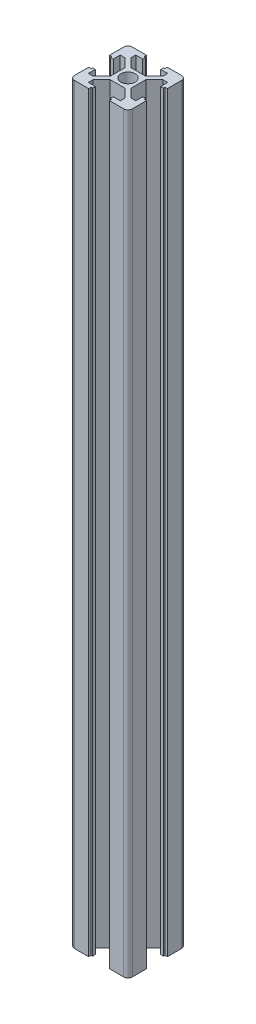
SolidWorks part; units mm, degrees
ref_plane "前视基准面" through (0, 0, 0) normal (0, 0, 1) x (1, 0, 0)
ref_plane "上视基准面" through (0, 0, 0) normal (0, 1, 0) x (1, 0, 0)
ref_plane "右视基准面" through (0, 0, 0) normal (1, 0, 0) x (0, 0, -1)
other "Configuration Table"
sketch "草图1" plane through (0, 0, 0) normal (0, 1, 0) x (1, 0, 0)
  line L0 (-4.4156, 1.3346) -> (-4.4156, 4.4346) construction
  line L1 (-4.4156, 3.874) -> (-4.4156, -1.2047)
  line L2 (1.7237, 4.9346) -> (-3.3549, 4.9346)
  line L3 (2.7844, -1.2047) -> (2.7844, 3.874)
  line L4 (-3.3549, -2.2654) -> (1.7237, -2.2654)
  line L5 (-10.8156, 1.3346) -> (9.1844, 1.3346) construction
  line L6 (-0.8156, 11.3346) -> (-0.8156, -8.6654) construction
  line L7 (-10.8156, 11.3346) -> (-0.8156, 1.3346) construction
  line L8 (-10.8156, 4.9346) -> (-4.4156, 4.9346) construction
  line L9 (-10.0156, 4.4346) -> (-3.9156, 4.4346) construction
  line L10 (-9.0156, 6.8346) -> (-6.3156, 6.8346) construction
  line L11 (-7.3763, 6.8346) -> (-4.4156, 3.874) construction
  line L12 (-10.8156, 9.8346) -> (-10.8156, 4.9346)
  line L13 (-10.8156, 4.9346) -> (-10.0156, 4.9346)
  line L14 (-10.0156, 4.9346) -> (-10.0156, 4.4346)
  line L15 (-10.0156, 4.4346) -> (-9.0156, 4.4346)
  line L16 (-9.0156, 4.4346) -> (-9.0156, 6.8346)
  line L17 (-9.0156, 6.8346) -> (-7.3763, 6.8346)
  line L18 (-7.3763, 6.8346) -> (-4.4156, 3.874)
  line L19 (-3.9156, 10.5346) -> (-3.9156, 9.5346)
  line L20 (-4.4156, 10.5346) -> (-3.9156, 10.5346)
  line L21 (-4.4156, 11.3346) -> (-4.4156, 10.5346)
  line L22 (-9.3156, 11.3346) -> (-4.4156, 11.3346)
  line L23 (-3.9156, 9.5346) -> (-6.3156, 9.5346)
  line L24 (-6.3156, 9.5346) -> (-6.3156, 7.8953)
  line L25 (-6.3156, 7.8953) -> (-3.3549, 4.9346)
  line L26 (9.1844, 11.3346) -> (-0.8156, 1.3346) construction
  line L27 (4.6844, 7.8953) -> (1.7237, 4.9346)
  line L28 (4.6844, 9.5346) -> (4.6844, 7.8953)
  line L29 (2.2844, 9.5346) -> (4.6844, 9.5346)
  line L30 (2.2844, 10.5346) -> (2.2844, 9.5346)
  line L31 (2.7844, 10.5346) -> (2.2844, 10.5346)
  line L32 (2.7844, 11.3346) -> (2.7844, 10.5346)
  line L33 (7.6844, 11.3346) -> (2.7844, 11.3346)
  line L34 (9.1844, 9.8346) -> (9.1844, 4.9346)
  line L35 (9.1844, 4.9346) -> (8.3844, 4.9346)
  line L36 (8.3844, 4.9346) -> (8.3844, 4.4346)
  line L37 (8.3844, 4.4346) -> (7.3844, 4.4346)
  line L38 (7.3844, 4.4346) -> (7.3844, 6.8346)
  line L39 (7.3844, 6.8346) -> (5.7451, 6.8346)
  line L40 (5.7451, 6.8346) -> (2.7844, 3.874)
  line L41 (9.1844, -8.6654) -> (-0.8156, 1.3346) construction
  line L42 (5.7451, -4.1654) -> (2.7844, -1.2047)
  line L43 (7.3844, -4.1654) -> (5.7451, -4.1654)
  line L44 (7.3844, -1.7654) -> (7.3844, -4.1654)
  line L45 (8.3844, -1.7654) -> (7.3844, -1.7654)
  line L46 (8.3844, -2.2654) -> (8.3844, -1.7654)
  line L47 (9.1844, -2.2654) -> (8.3844, -2.2654)
  line L48 (9.1844, -7.1654) -> (9.1844, -2.2654)
  line L49 (7.6844, -8.6654) -> (2.7844, -8.6654)
  line L50 (2.7844, -8.6654) -> (2.7844, -7.8654)
  line L51 (2.7844, -7.8654) -> (2.2844, -7.8654)
  line L52 (2.2844, -7.8654) -> (2.2844, -6.8654)
  line L53 (2.2844, -6.8654) -> (4.6844, -6.8654)
  line L54 (4.6844, -6.8654) -> (4.6844, -5.226)
  line L55 (4.6844, -5.226) -> (1.7237, -2.2654)
  line L56 (-10.8156, -8.6654) -> (-0.8156, 1.3346) construction
  line L57 (-6.3156, -5.226) -> (-3.3549, -2.2654)
  line L58 (-6.3156, -6.8654) -> (-6.3156, -5.226)
  line L59 (-3.9156, -6.8654) -> (-6.3156, -6.8654)
  line L60 (-3.9156, -7.8654) -> (-3.9156, -6.8654)
  line L61 (-4.4156, -7.8654) -> (-3.9156, -7.8654)
  line L62 (-4.4156, -8.6654) -> (-4.4156, -7.8654)
  line L63 (-9.3156, -8.6654) -> (-4.4156, -8.6654)
  line L64 (-10.8156, -7.1654) -> (-10.8156, -2.2654)
  line L65 (-10.8156, -2.2654) -> (-10.0156, -2.2654)
  line L66 (-10.0156, -2.2654) -> (-10.0156, -1.7654)
  line L67 (-10.0156, -1.7654) -> (-9.0156, -1.7654)
  line L68 (-9.0156, -1.7654) -> (-9.0156, -4.1654)
  line L69 (-9.0156, -4.1654) -> (-7.3763, -4.1654)
  line L70 (-7.3763, -4.1654) -> (-4.4156, -1.2047)
  arc A0 (-10.8156, 9.8346) -> (-9.3156, 11.3346) centre (-9.3156, 9.8346) cw
  circle A1 centre (-0.8156, 1.3346) radius 2.5
  arc A2 (7.6844, 11.3346) -> (9.1844, 9.8346) centre (7.6844, 9.8346) cw
  arc A3 (9.1844, -7.1654) -> (7.6844, -8.6654) centre (7.6844, -7.1654) cw
  arc A4 (-9.3156, -8.6654) -> (-10.8156, -7.1654) centre (-9.3156, -7.1654) cw
  point P13 (-0.8156, 1.3346)
  point P84 (-0.8156, 1.3346)
  dimension "D8" = 1.5
  dimension "D9" = 5
  dimension "D1" = 20
  dimension "D2" = 6.2
  dimension "D3" = 7.2
  dimension "D4" = 11
  dimension "D5" = 1.5
  dimension "D6" = 0.8
  dimension "D7" = 1.8
  dimension "D10" = 7.2
extrude "凸台-拉伸1" add sketch "草图1" along normal blind 260
